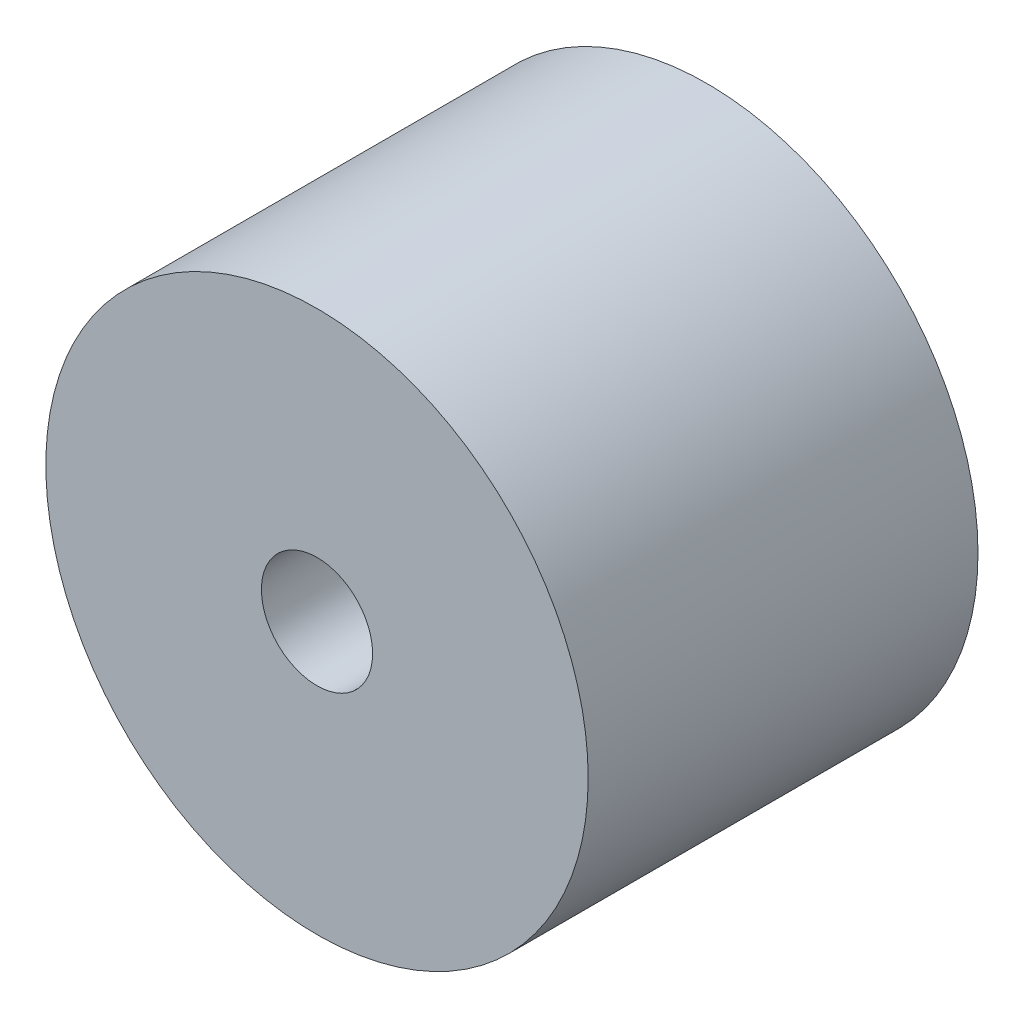
SolidWorks part; units mm, degrees
ref_plane "Front Plane" through (0, 0, 0) normal (0, 0, 1) x (1, 0, 0)
ref_plane "Top Plane" through (0, 0, 0) normal (0, 1, 0) x (1, 0, 0)
ref_plane "Right Plane" through (0, 0, 0) normal (1, 0, 0) x (0, 0, -1)
ref_axis "X-Axis" through (-88.99, 0, 0) along (1, 0, 0)
ref_axis "Y-Axis" through (0, 55, 0) along (0, -1, 0)
ref_axis "Z-Axis" through (0, 0, -88.99) along (0, 0, 1)
sketch "Sketch1" plane through (0, 0, 0) normal (0, 0, 1) x (1, 0, 0)
  circle A0 centre (0, 0) radius 20
  dimension "D1" = 40
extrude "Boss-Extrude1" add sketch "Sketch1" along normal blind 28.75
sketch "Sketch3" plane through (0, 0, 28.75) normal (0, 0, 1) x (1, 0, 0)
  circle A0 centre (0, 0) radius 4.1
  dimension "D1" = 8.2
extrude "Cut-Extrude1" cut sketch "Sketch3" against normal through all
